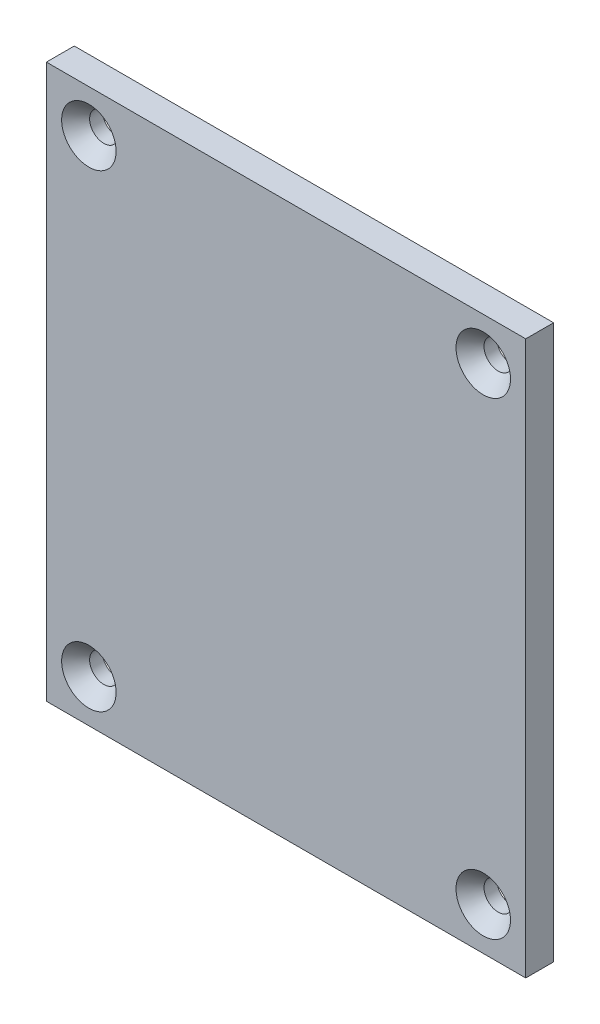
SolidWorks part; units mm, degrees
ref_plane "Front" through (0, 0, 0) normal (0, 0, 1) x (1, 0, 0)
ref_plane "Top" through (0, 0, 0) normal (0, 1, 0) x (1, 0, 0)
ref_plane "Right" through (0, 0, 0) normal (1, 0, 0) x (0, 0, -1)
sketch "Sketch1" plane through (0, 0, 0) normal (0, 0, 1) x (1, 0, 0)
  line L1 (-43, -49.657) -> (43, -49.657)
  line L2 (-43, -49.657) -> (-43, 49.657)
  line L3 (-43, 49.657) -> (43, 49.657)
  line L4 (43, -49.657) -> (43, 49.657)
  line L5 (-43, -49.657) -> (43, 49.657) construction
  line L6 (-43, 49.657) -> (43, -49.657) construction
  point P0 (0, 0)
  dimension "D1" = 86
  dimension "D2" = 99.314
extrude "Boss-Extrude1" add sketch "Sketch1" along normal blind 5
hole_wizard "CSK for #10 Flat Head Machine Screw1" positions "Sketch2" profile "Sketch3" countersink size "#10" standard "ANSI Inch" end condition up to next
sketch "Sketch2" plane through (0, 0, 5) normal (0, 0, 1) x (1, 0, 0)
  line L0 (43, 49.657) -> (-43, 49.657) construction
  line L1 (-43, 49.657) -> (-43, -49.657) construction
  line L2 (43, -49.657) -> (43, 49.657) construction
  line L3 (-43, -49.657) -> (43, -49.657) construction
  point P0 (-35.38, 42.037)
  point P2 (35.38, 42.037)
  point P4 (-35.38, -42.037)
  point P6 (35.38, -42.037)
  dimension "D1" = 7.62
  dimension "D2" = 7.62
  dimension "D3" = 7.62
  dimension "D4" = 7.62
sketch "Sketch3" plane through (-35.38, 42.037, 5) normal (1, 0, 0) x (0, -1, 0)
  line L0 (0, 0) -> (0, 5)
  line L1 (0, 5) -> (2.5527, 5)
  line L2 (2.5527, 5) -> (2.5527, 2.6882)
  line L3 (2.5527, 2.6882) -> (4.8895, 0)
  line L5 (4.8895, 0) -> (0, 0)
  line L6 (-2.5527, 2.6882) -> (-4.8895, 0) construction
  line L11 (0, -6.35) -> (0, 107.95) construction
  dimension "Thru Hole Dia." = 5.1054
  dimension "Thru Hole Depth" = 5
  dimension "Near C'Sink Dia." = 9.779
  dimension "Near C'Sink Angle" = 82
equation "\"PCB Width\"= 1940mil"
equation "\"PCB Height\"= 2210mil"
equation "\"PCB Thickness\"= 63mil"
equation "\"Motor Bearing Diameter\"= 12mm"
equation "\"Motor Bearing Length\"= 5mm"
equation "\"Motor Body Front Diameter\"= 37mm"
equation "\"Motor Body Front Length\"= 30mm"
equation "\"Motor Body Back Length\"= 33.3mm"
equation "\"Motor PCD\"= 31mm"
equation "\"Large PVC Fittings Wall Thickness\"= 15in / 64"
equation "\"Large PVC Pipe Outer Diameter\"= 3.5in"
equation "\"Box Width\"= 2 * \"Motor Bearing Length\" + \"Motor Body Front Length\" + \"Motor Body Back Length\" + 0.5in"
equation "\"Box Hole Center to Edge Distance\"= 300mil"
equation "\"Box Ceiling and Floor Thickness\"= 2 * \"Box Hole Center to Edge Distance\""
equation "\"Box Height\"= 2 * \"Box Ceiling and Floor Thickness\" + \"PCB Height\" + 0.5in"
equation "\"Box Back Depth\"= \"Large PVC Fittings Wall Thickness\" + \"Large PVC Pipe Outer Diameter\" / 2 + \"Motor Body Front Diameter\" / 2"
equation "\"D1@Sketch1\"=\"Box Width\""
equation "\"D2@Sketch1\"=\"Box Height\""
equation "\"D1@Boss-Extrude1\"=\"Motor Bearing Length\""
equation "\"D1@Sketch2\"=\"Box Hole Center to Edge Distance\""
equation "\"D2@Sketch2\"=\"Box Hole Center to Edge Distance\""
equation "\"D3@Sketch2\"=\"Box Hole Center to Edge Distance\""
equation "\"D4@Sketch2\"=\"Box Hole Center to Edge Distance\""
